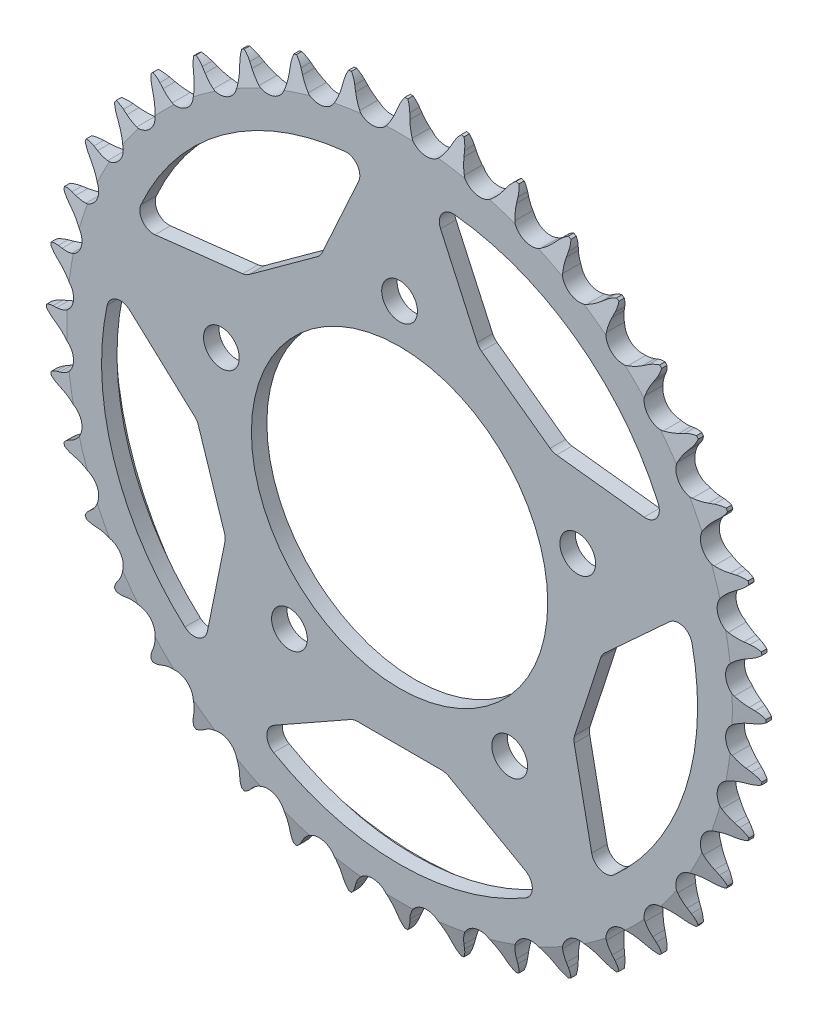
SolidWorks part; units mm, degrees
ref_plane "Front Plane" through (0, 0, 0) normal (0, 0, 1) x (1, 0, 0)
ref_plane "Top Plane" through (0, 0, 0) normal (0, 1, 0) x (1, 0, 0)
ref_plane "Right Plane" through (0, 0, 0) normal (1, 0, 0) x (0, 0, -1)
sketch "Sketch0" plane through (0, 0, 0) normal (0, 0, 1) x (1, 0, 0)
  line L0 (7.9375, -100.8555) -> (0, 0) construction
  line L1 (0, 0) -> (23.6171, -98.3721) construction
  line L2 (0, 0) -> (-7.9375, -100.8555) construction
  line L3 (7.9375, -100.8555) -> (23.6171, -98.3721) construction
  line L4 (7.9375, -100.8555) -> (-7.9375, -100.8555) construction
  line L5 (14.4905, -102.0307) -> (13.8894, -100.7054)
  line L6 (7.9375, -100.8555) -> (0, -101.4802) construction
  line L7 (1.649, -103.0413) -> (2.0354, -101.6384)
  line L8 (0, -100.8555) -> (0, -105.618) construction
  line L9 (11.8193, -97.4811) -> (1.8032, -106.1879) construction
  line L10 (0, 0) -> (0, -100.8555) construction
  line L11 (13.8894, -100.7054) -> (1.8032, -106.1879) construction
  line L12 (0, -105.618) -> (0, -106.1687) construction
  line L13 (21.9864, -98.6304) -> (14.4905, -102.0307) construction
  circle A0 centre (0, 0) radius 105.618 construction
  circle A1 centre (0, 0) radius 101.1674 construction
  arc A2 (-6.7986, -109.0706) -> (23.7773, -106.6642) centre (0, 0) ccw
  circle A3 centre (0, 0) radius 106.1687 construction
  circle A4 centre (7.9375, -100.8555) radius 5.08 construction
  arc A7 (11.8193, -97.4811) -> (3.5756, -98.1299) centre (7.9375, -100.8555) ccw
  circle A8 centre (7.9375, -100.8555) radius 5.1435 construction
  arc A9 (14.4905, -102.0307) -> (23.7773, -106.6642) centre (21.9864, -98.6304) ccw
  arc A10 (13.8894, -100.7054) -> (11.8193, -97.4811) centre (1.8032, -106.1879) ccw
  arc A11 (1.649, -103.0413) -> (-6.7986, -109.0706) centre (-6.2865, -100.8555) cw
  arc A12 (2.0354, -101.6384) -> (3.5756, -98.1299) centre (14.8304, -105.1627) cw
  dimension "D1" = 5.1435
  dimension "R" = 5.1435
sketch "Sketch1" plane through (0, 0, 0) normal (1, 0, 0) x (0, 0, -1)
  line L0 (2.7686, 0) -> (-2.7686, 0)
  line L1 (-2.7686, 0) -> (-2.7686, 97.6805)
  line L2 (-2.7686, 97.6805) -> (-0.7842, 105.618)
  line L3 (-0.7842, 105.618) -> (0.7842, 105.618)
  line L4 (0.7842, 105.618) -> (2.7686, 97.6805)
  line L5 (2.7686, 97.6805) -> (2.7686, 0)
  line L7 (0, 105.618) -> (0, 0) construction
  line L8 (-2.7686, 97.6805) -> (2.7686, 97.6805) construction
  line L9 (0, 105.618) -> (0, -105.618) construction
  line L10 (-2.7686, 97.6805) -> (-2.7686, 105.618) construction
  line L11 (-2.7686, 105.618) -> (-0.7842, 105.618) construction
  line L12 (0.7842, 105.618) -> (2.7686, 105.618) construction
  line L13 (2.7686, 105.618) -> (2.7686, 97.6805) construction
revolve "Revolve1" add sketch "Sketch1" angle 360 mid plane about L0
extrude "Cut-Extrude1" cut sketch "Sketch0" against normal through all and the other way through all
pattern_circular "CirPattern1" count 40 over 360 about axis through (0, 0, -2.7686) along (0, 0, -1) of "Cut-Extrude1"
sketch "Sketch2" plane through (0, 0, 0) normal (0, 0, 1) x (1, 0, 0)
  circle A0 centre (0, 0) radius 9.1281 construction
  circle A1 centre (0, 0) radius 30.1625
  circle A2 centre (0, 0) radius 105.664 construction
  dimension "Bore" = 18.2562
  dimension "Hub Dia." = 60.325
  dimension "OD" = 211.328
sketch "Sketch3" plane through (0, 0, 0) normal (0, 0, 1) x (1, 0, 0)
  circle A0 centre (0, 0) radius 9.1281 construction
  circle A1 centre (0, 0) radius 9.1281
  circle A2 centre (0, 0) radius 105.664 construction
  circle A3 centre (0, 0) radius 105.664
extrude "Cut-Extrude2" cut sketch "Sketch3" along normal through all and the other way through all flip side to cut
sketch "Sketch4" plane through (0, 0, -2.7686) normal (0, 0, -1) x (-1, 0, 0)
  line L0 (12.4287, -58.0608) -> (-12.4287, -58.0608)
  line L1 (-14.3964, -58.5783) -> (-36.9361, -71.3133)
  line L2 (0, -58.0608) -> (0, -88.2014) construction
  line L3 (14.3964, -58.5783) -> (36.9361, -71.3133)
  line L16 (-34.9684, -74.7959) -> (0, -74.7959) construction
  line L17 (34.9684, -74.7959) -> (0, -74.7959) construction
  line L18 (-51.3784, -29.7622) -> (-59.0598, -6.1213)
  line L19 (-60.16, -4.4099) -> (-79.2369, 13.0913)
  line L20 (-51.2625, -31.7935) -> (-56.4091, -57.1654)
  line L21 (-44.1824, 39.6668) -> (-24.0722, 54.2776)
  line L22 (-22.7845, 55.8528) -> (-12.035, 79.4042)
  line L23 (-46.0784, 38.9288) -> (-71.7989, 35.9832)
  line L24 (24.0722, 54.2776) -> (44.1824, 39.6668)
  line L25 (46.0784, 38.9288) -> (71.7989, 35.9832)
  line L26 (22.7845, 55.8528) -> (12.035, 79.4042)
  line L27 (59.0598, -6.1213) -> (51.3784, -29.7622)
  line L28 (51.2625, -31.7935) -> (56.4091, -57.1654)
  line L29 (60.16, -4.4099) -> (79.2369, 13.0913)
  circle A0 centre (0, 0) radius 43.5
  circle A1 centre (0, 0) radius 55 construction
  circle A2 centre (0, 0) radius 101.6
  circle A3 centre (0, 0) radius 115.5885 construction
  circle A4 centre (0, 55) radius 5.25
  arc A9 (-36.975, -78.2562) -> (0, -88.2014) centre (0, -14.4944) ccw
  arc A10 (36.975, -78.2562) -> (0, -88.2014) centre (0, -14.4944) cw
  arc A11 (-12.4287, -58.0608) -> (-14.3964, -58.5783) centre (-12.4287, -62.0608) ccw
  arc A12 (14.3964, -58.5783) -> (12.4287, -58.0608) centre (12.4287, -62.0608) ccw
  arc A13 (36.9361, -71.3133) -> (36.975, -78.2562) centre (34.9684, -74.7959) cw
  arc A14 (-36.9361, -71.3133) -> (-36.975, -78.2562) centre (-34.9684, -74.7959) ccw
  circle A39 centre (0, 0) radius 9.1281 construction
  circle A40 centre (52.3081, 16.9959) radius 5.25
  circle A41 centre (32.3282, -44.4959) radius 5.25
  circle A42 centre (-32.3282, -44.4959) radius 5.25
  circle A43 centre (-52.3081, 16.9959) radius 5.25
  arc A44 (-59.0598, -6.1213) -> (-60.16, -4.4099) centre (-62.864, -7.3574) ccw
  arc A45 (-79.2369, 13.0913) -> (-85.852, 10.9829) centre (-81.941, 10.1438) ccw
  arc A46 (-85.852, 10.9829) -> (-83.8845, -27.2557) centre (-13.785, -4.479) ccw
  arc A47 (-63.0001, -59.3479) -> (-83.8845, -27.2557) centre (-13.785, -4.479) cw
  arc A48 (-56.4091, -57.1654) -> (-63.0001, -59.3479) centre (-60.3293, -56.3702) cw
  arc A49 (-51.2625, -31.7935) -> (-51.3784, -29.7622) centre (-55.1827, -30.9983) ccw
  arc A50 (-24.0722, 54.2776) -> (-22.7845, 55.8528) centre (-26.4234, 57.5137) ccw
  arc A51 (-12.035, 79.4042) -> (-16.0844, 85.044) centre (-15.6739, 81.0651) ccw
  arc A52 (-16.0844, 85.044) -> (-51.8435, 71.3564) centre (-8.5196, 11.7262) ccw
  arc A53 (-75.9113, 41.5772) -> (-51.8435, 71.3564) centre (-8.5196, 11.7262) cw
  arc A54 (-71.7989, 35.9832) -> (-75.9113, 41.5772) centre (-72.254, 39.9572) cw
  arc A55 (-46.0784, 38.9288) -> (-44.1824, 39.6668) centre (-46.5335, 42.9028) ccw
  arc A56 (44.1824, 39.6668) -> (46.0784, 38.9288) centre (46.5335, 42.9028) ccw
  arc A57 (71.7989, 35.9832) -> (75.9113, 41.5772) centre (72.254, 39.9572) ccw
  arc A58 (75.9113, 41.5772) -> (51.8435, 71.3564) centre (8.5196, 11.7262) ccw
  arc A59 (16.0844, 85.044) -> (51.8435, 71.3564) centre (8.5196, 11.7262) cw
  arc A60 (12.035, 79.4042) -> (16.0844, 85.044) centre (15.6739, 81.0651) cw
  arc A61 (22.7845, 55.8528) -> (24.0722, 54.2776) centre (26.4234, 57.5137) ccw
  arc A62 (51.3784, -29.7622) -> (51.2625, -31.7935) centre (55.1827, -30.9983) ccw
  arc A63 (56.4091, -57.1654) -> (63.0001, -59.3479) centre (60.3293, -56.3702) ccw
  arc A64 (63.0001, -59.3479) -> (83.8845, -27.2557) centre (13.785, -4.479) ccw
  arc A65 (85.852, 10.9829) -> (83.8845, -27.2557) centre (13.785, -4.479) cw
  arc A66 (79.2369, 13.0913) -> (85.852, 10.9829) centre (81.941, 10.1438) cw
  arc A67 (60.16, -4.4099) -> (59.0598, -6.1213) centre (62.864, -7.3574) ccw
  point P18 (0, 0)
  point P35 (0, 0)
  point P92 (-19.3373, 37.6343)
  point P99 (0, 0)
  dimension "D1" = 110
  dimension "D2" = 87
  dimension "D3" = 10.5
  dimension "D4" = 203.2
  dimension "D5" = 4
  dimension "D6" = 5
  dimension "D7" = 5
extrude "Cut-Extrude3" cut sketch "Sketch4" against normal through all contours L20 A49 L18 A44 L19 A45 A46 A47 A48 | L23 A55 L21 A50 L22 A51 A52 A53 A54 | L26 A61 L24 A56 L25 A57 A58 A59 A60 | L29 A67 L27 A62 L28 A63 A64 A65 A66 | L1 A14 A9 A10 A13 L3 A12 L0 A11 | A0 | A41 | A40 | A4 | A43 | A42 region at (0, -73.4068, -2.7686) region at (69.814, -22.6839, -2.7686) region at (43.1474, 59.3873, -2.7686) region at (-43.1474, 59.3873, -2.7686) region at (-69.814, -22.6839, -2.7686) region at (0, 0, -2.7686) region at (0, 55, -2.7686) region at (-52.3081, 16.9959, -2.7686) region at (-32.3282, -44.4959, -2.7686) region at (32.3282, -44.4959, -2.7686) region at (52.3081, 16.9959, -2.7686)
sketch "Sketch5" plane through (0, 0, -2.7686) normal (0, 0, -1) x (-1, 0, 0)
  circle A0 centre (0, 0) radius 88.9
  dimension "D1" = 177.8
extrude "Cut-Extrude4" cut sketch "Sketch5" against normal blind 1
equation "\"360/N@Sketch0\" = 360/\"Teeth@CirPattern1\""
equation "\"Ds@Sketch0\" = 1.005 * \"Dr@Sketch0\" + 0.003"
equation "\"R@Sketch0\" = 1/2 * \"Ds@Sketch0\""
equation "\"A@Sketch0\" = 35 +  ( 60 / \"Teeth@CirPattern1\" ) "
equation "\"B@Sketch0\" = 18 -  ( 56 / \"Teeth@CirPattern1\" )"
equation "\"ac@Sketch0\" = 0.8 * \"Dr@Sketch0\""
equation "\"ab@Sketch0\" = 1.4 * \"Dr@Sketch0\""
equation "\"J@Sketch0\" = 0.3 * \"Pitch@Sketch0\""
equation "\"h@Sketch1\" = \"Pitch@Sketch0\" / 2"
equation "\"g@Sketch1\" = \"h@Sketch1\" / 4"
